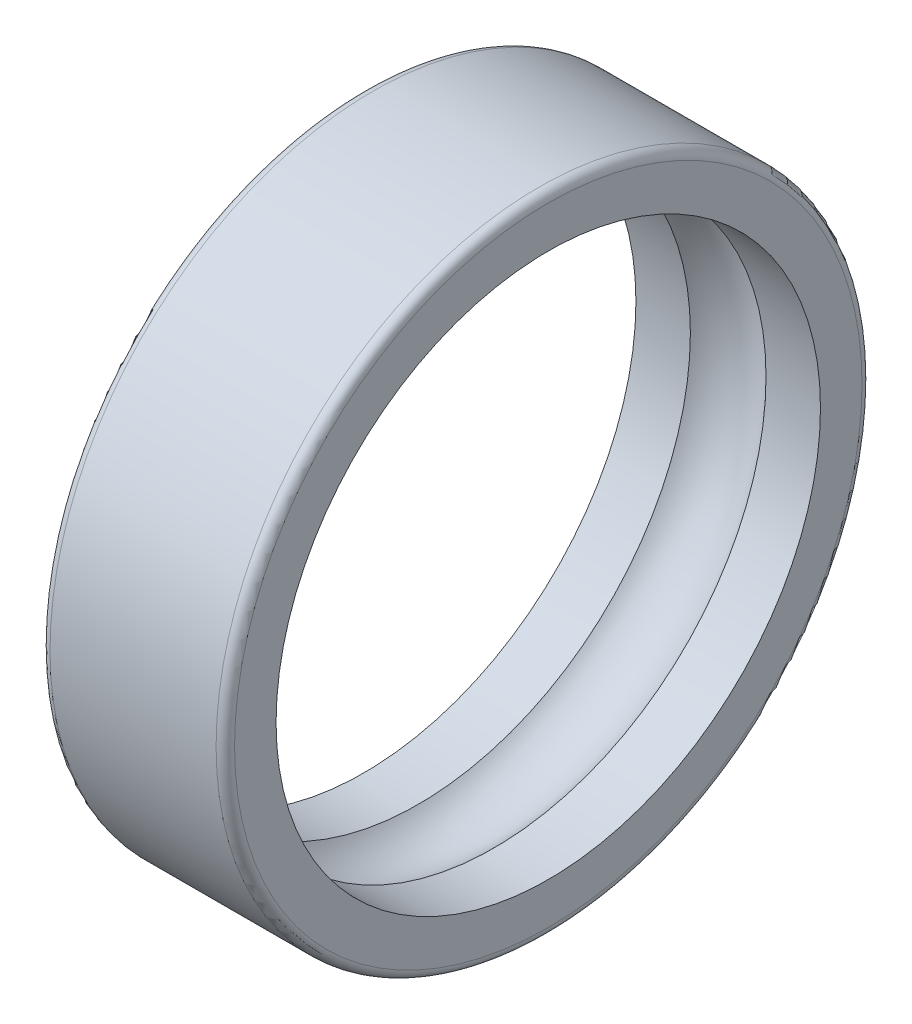
SolidWorks part; units mm, degrees
ref_plane "Plan1" through (0, 0, 0) normal (0, 0, 1) x (1, 0, 0)
ref_plane "Plan2" through (0, 0, 0) normal (0, 1, 0) x (1, 0, 0)
ref_plane "Plan3" through (0, 0, 0) normal (1, 0, 0) x (0, 0, -1)
ref_axis "Axe1" through (-50, 0, 0) along (1, 0, 0)
sketch "Esquisse1" plane through (0, 0, 0) normal (0, 1, 0) x (1, 0, 0)
  line L0 (0, 20.4) -> (0, 10.6) construction
  line L1 (12, 17.7) -> (0, 17.7) construction
  line L2 (12, 20.4) -> (12, 10.6) construction
  line L3 (0.6, 21) -> (11.4, 21) construction
  line L4 (0, 20.4) -> (0, 17.7)
  line L5 (12, 17.7) -> (8.4597, 17.7)
  line L6 (0, 0) -> (12, 0) construction
  line L7 (-50, 0) -> (200, 0) construction
  line L8 (12, 20.4) -> (12, 17.7)
  line L9 (0.6, 21) -> (11.4, 21)
  line L10 (3.5403, 17.7) -> (0, 17.7)
  arc A0 (0.6, 21) -> (0, 20.4) centre (0.6, 20.4) ccw construction
  circle A1 centre (6, 15.5) radius 3.3 construction
  arc A3 (12, 20.4) -> (11.4, 21) centre (11.4, 20.4) ccw construction
  arc A4 (0.6, 21) -> (0, 20.4) centre (0.6, 20.4) ccw
  arc A5 (8.4597, 17.7) -> (3.5403, 17.7) centre (6, 15.5) ccw
  arc A6 (12, 20.4) -> (11.4, 21) centre (11.4, 20.4) ccw
revolve "Base-Révolution" add sketch "Esquisse1" angle 360 about L6
